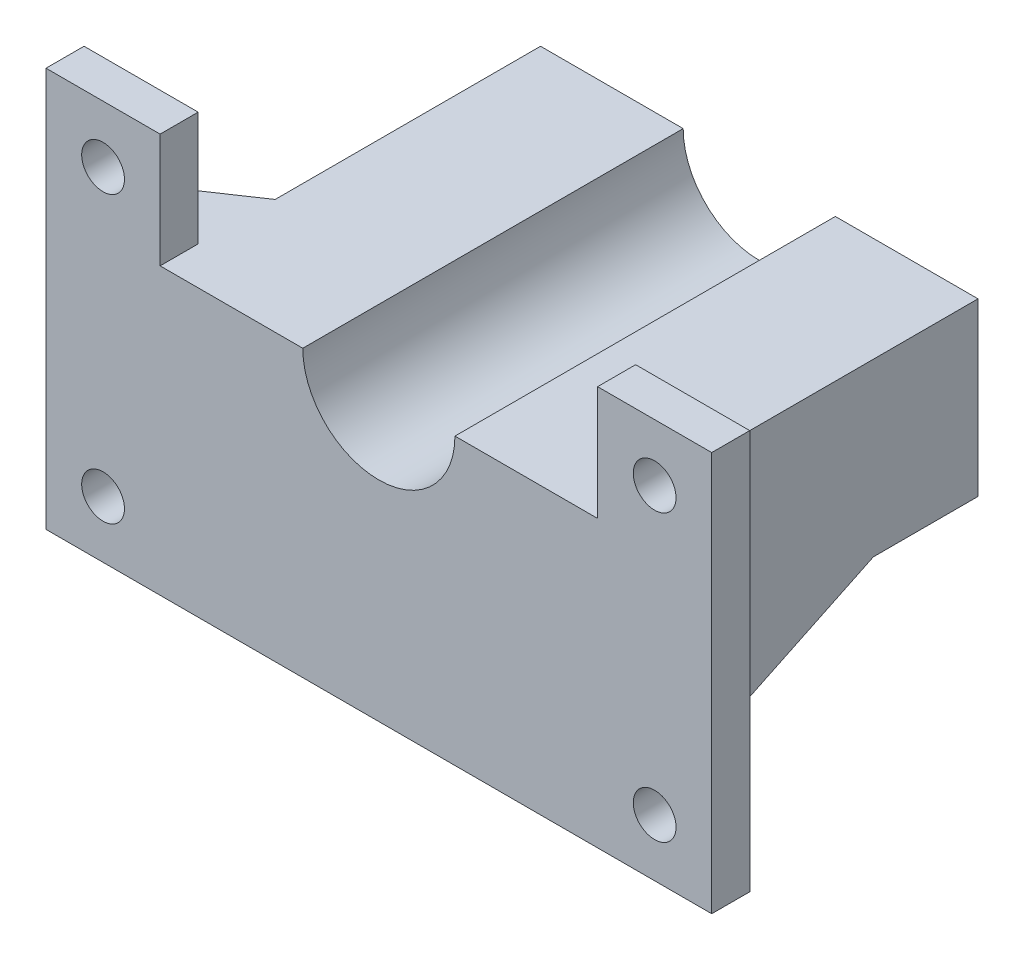
SolidWorks part; units mm, degrees
ref_plane "Piano frontale" through (0, 0, 0) normal (0, 0, 1) x (1, 0, 0)
ref_plane "Piano superiore" through (0, 0, 0) normal (0, 1, 0) x (1, 0, 0)
ref_plane "Piano destro" through (0, 0, 0) normal (1, 0, 0) x (0, 0, -1)
sketch "Schizzo1" plane through (0, 0, 0) normal (0, 0, 1) x (1, 0, 0)
  line L0 (-23, 0) -> (23, 0)
  line L1 (23, 0) -> (23, 18)
  line L2 (23, 18) -> (8, 18)
  line L3 (-23, 0) -> (-23, 18)
  line L4 (-23, 18) -> (-8, 18)
  line L5 (-8, 18) -> (0, 18) construction
  line L6 (-23, 18) -> (-23, 30)
  line L7 (-23, 30) -> (-35, 30)
  line L8 (-35, 30) -> (-35, -12)
  line L9 (-35, -12) -> (35, -12)
  line L10 (35, -12) -> (35, 30)
  line L11 (35, 30) -> (23, 30)
  line L12 (23, 30) -> (23, 18)
  arc A0 (-8, 18) -> (8, 18) centre (0, 18) ccw
  point P6 (0, 0)
  dimension "D1" = 16
  dimension "D2" = 18
  dimension "D3" = 15
  dimension "D4" = 12
  dimension "D5" = 12
  dimension "D6" = 12
extrude "Estrusione-Estrusione1" add sketch "Schizzo1" along normal blind 4 contours L11 L12 L1 L0 L3 L6 L7 L8 L9 L10 | A0 L4 L3 L0 L1 L2 region at (0, 8.2255, 0) region at (0, -0.8163, 0)
extrude "Estrusione-Estrusione2" add sketch "Schizzo1<3>" against normal blind 36 contours A0 L4 L3 L0 L1 L2 region at (0, 8.2255, 0)
sketch "Schizzo1<3>" plane through (0, 0, 0) normal (0, 0, 1) x (1, 0, 0) same geometry as "Schizzo1"
sketch "Schizzo6" plane through (23, 0, 0) normal (1, 0, 0) x (0, 0, -1)
  line L0 (0, 0) -> (25, 0)
  line L1 (36, 0) -> (0, 0) construction
  line L2 (25, 0) -> (0, -12)
  line L3 (0, -12) -> (0, 0)
  dimension "D1" = 25
extrude "Estrusione-Estrusione3" add sketch "Schizzo6" against normal up to vertex (46 mm away) up to point (-23, 0, -36)
chamfer "Smusso3" distance 8.0941 angle 56 1 edges at (-23, 3, 0) first distance on face at (-23, 4.8, -19.4)
chamfer "Smusso2" distance 8.0941 angle 56 1 edges at (23, 3, 0) first distance on face at (23, 4.8, -19.4)
sketch "Schizzo2" [suppressed] plane through (9.3809, 0, -13.9078) normal (0.5592, 0, -0.829) x (-0.829, 0, -0.5592)
sketch "Schizzo4" plane through (0, 0, -36) normal (0, 0, -1) x (-1, 0, 0)
  line L2 (-35, -12) -> (-23, 0) construction
  line L4 (23, 0) -> (35, -12) construction
  line L6 (23, 0) -> (-23, 0) construction
  point P0 (-29, -6)
  point P4 (29, -6)
  point P19 (-29, -6)
  point P27 (29, -6)
hole_wizard "Foro lamato per Vite M4 a testa cilindrica piana-1" positions "Schizzo4" profile "Schizzo3" counterbore size "M4" standard "ISO"
sketch "Schizzo3" plane through (29, -6, -36) normal (1, 0, 0) x (0, 1, 0)
  line L0 (0, 0) -> (0, 51.3519)
  line L1 (0, 51.3519) -> (2.25, 50)
  line L2 (2.25, 50) -> (2.25, 35.6)
  line L3 (2.25, 35.6) -> (4, 35.6)
  line L4 (4, 35.6) -> (4, 0)
  line L5 (4, 0) -> (0, 0)
  line L10 (0, 51.3519) -> (-2.25, 50) construction
  line L11 (0, -6.35) -> (0, 107.95) construction
  dimension "Hole Dia." = 4.5
  dimension "Hole Depth" = 50
  dimension "C'Bore Dia." = 8
  dimension "C'Bore Depth" = 35.6
  dimension "Drill Angle" = 118
hole_wizard "Foro per Vite M4-1" positions "Schizzo3D1" profile "Schizzo5" hole size "M4" standard "ISO"
sketch3d "Schizzo3D1"
  line L0 (23, 18, 0) -> (35, 30, 0) construction
  line L2 (35, 18, 0) -> (23, 30, 0) construction
  line L4 (-35, 30, 0) -> (-23, 18, 0) construction
  line L6 (-23, 30, 0) -> (-35, 18, 0) construction
  line L8 (23, 18, 0) -> (35, 18, 0) construction
  line L10 (35, 18, 0) -> (35, 30, 0) construction
  line L11 (-23, 18, 0) -> (-35, 18, 0) construction
  line L13 (-35, 30, 0) -> (-35, 18, 0) construction
  point P0 (29, 24, 0)
  point P2 (-29, 24, 0)
  point P16 (29, 24, 0)
  point P27 (-29, 24, 0)
sketch "Schizzo5" plane through (29, 24, 0) normal (1, 0, 0) x (0, 1, 0)
  line L0 (0, 0) -> (0, 51.3519)
  line L1 (0, 51.3519) -> (2.25, 50)
  line L2 (2.25, 50) -> (2.25, 0)
  line L5 (2.25, 0) -> (0, 0)
  line L10 (0, 51.3519) -> (-2.25, 50) construction
  line L11 (0, -6.35) -> (0, 107.95) construction
  dimension "Hole Dia." = 4.5
  dimension "Hole Depth" = 50
  dimension "Drill Angle" = 118
